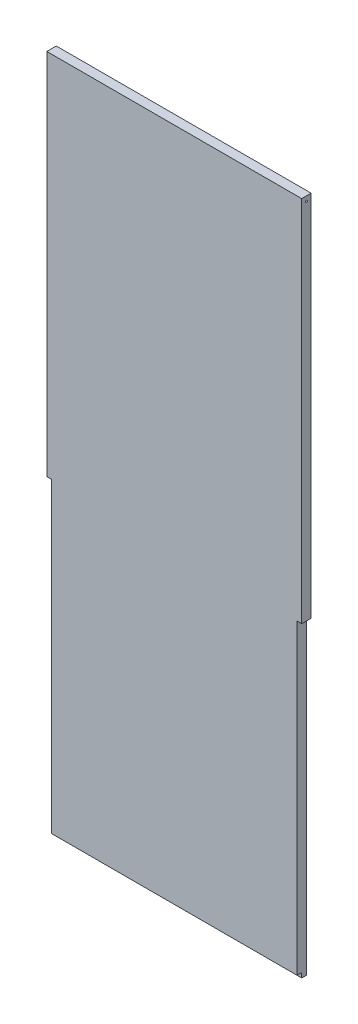
SolidWorks part; units mm, degrees
ref_plane "Front Plane" through (0, 0, 0) normal (0, 0, 1) x (1, 0, 0)
ref_plane "Top Plane" through (0, 0, 0) normal (0, 1, 0) x (1, 0, 0)
ref_plane "Right Plane" through (0, 0, 0) normal (1, 0, 0) x (0, 0, -1)
sketch "Sketch1" plane through (0, 0, 0) normal (0, 0, 1) x (1, 0, 0)
  line L0 (0, 419.1) -> (-6.35, 419.1)
  line L1 (0, 0) -> (330.2, 0)
  line L2 (0, 0) -> (0, 419.1)
  line L4 (330.2, 0) -> (330.2, 419.1)
  line L5 (-6.35, 419.1) -> (-6.35, 914.4)
  line L7 (165.1, 914.4) -> (165.1, 50914.4) construction
  line L9 (330.2, 419.1) -> (336.55, 419.1)
  line L10 (336.55, 419.1) -> (336.55, 914.4)
  line L11 (-6.35, 914.4) -> (336.55, 914.4)
  dimension "D1" = 330.2
  dimension "D2" = 914.4
  dimension "D3" = 6.35
  dimension "D4" = 495.3
extrude "Boss-Extrude1" add sketch "Sketch1" along normal blind 12.7
sketch "Sketch2" plane through (0, 0, 12.7) normal (0, 0, 1) x (1, 0, 0)
  line L0 (0, 419.1) -> (0, 0) construction
  line L1 (0, 6.35) -> (330.2, 6.35)
  line L2 (0, 6.35) -> (0, 0)
  line L3 (0, 0) -> (330.2, 0)
  line L4 (330.2, 6.35) -> (330.2, 0)
  line L5 (330.2, 0) -> (330.2, 419.1) construction
  line L6 (0, 0) -> (330.2, 0) construction
  dimension "D1" = 6.35
extrude "Cut-Extrude1" cut sketch "Sketch2" against normal blind 6.35
sketch "Sketch3" plane through (-6.35, 0, 0) normal (-1, 0, 0) x (0, 0, 1)
  line L0 (12.7, 914.4) -> (12.7, 419.1) construction
  line L1 (12.7, 914.4) -> (0, 914.4) construction
  circle A0 centre (6.35, 908.05) radius 1.27
  dimension "D1" = 2.54
  dimension "D2" = 6.35
  dimension "D3" = 6.35
extrude "Cut-Extrude2" cut sketch "Sketch3" against normal through all
